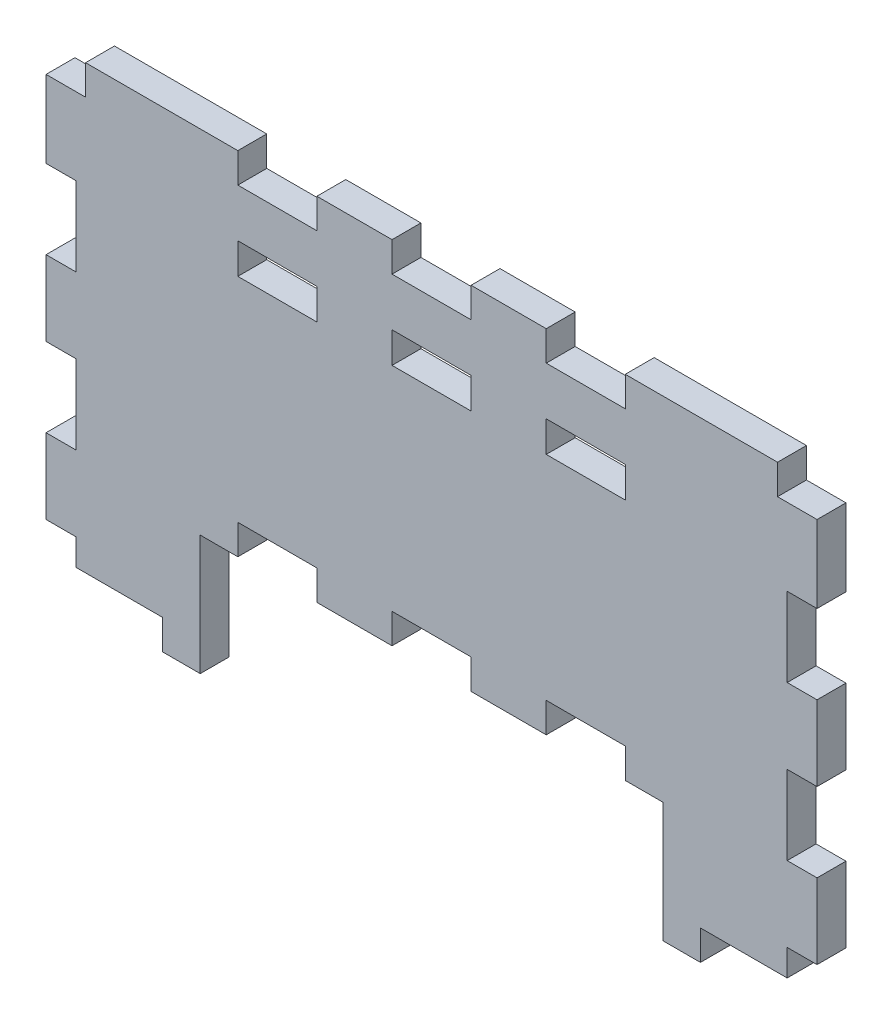
SolidWorks part; units mm, degrees
ref_plane "Front Plane" through (0, 0, 0) normal (0, 0, 1) x (1, 0, 0)
ref_plane "Top Plane" through (0, 0, 0) normal (0, 1, 0) x (1, 0, 0)
ref_plane "Right Plane" through (0, 0, 0) normal (1, 0, 0) x (0, 0, -1)
sketch "Sketch1" plane through (0, 0, 0) normal (0, 0, 1) x (1, 0, 0)
  line L0 (80, 3.175) -> (0, 3.175) construction
  line L1 (0, 52.125) -> (80, 52.125)
  line L2 (0, 52.125) -> (0, 3.175)
  line L3 (0, 3.175) -> (80, 3.175) construction
  line L4 (80, 52.125) -> (80, 3.175)
  line L5 (80, 52.125) -> (0, 52.125) construction
  line L6 (0, 52.125) -> (0, 3.175) construction
  line L7 (80, 52.125) -> (80, 3.175) construction
  line L8 (3, 49.125) -> (77, 49.125) construction
  line L9 (77, 49.125) -> (77, 6.175) construction
  line L10 (3, 6.175) -> (77, 6.175) construction
  line L11 (3, 49.125) -> (3, 6.175) construction
  line L12 (77, 49.125) -> (3, 49.125) construction
  line L13 (0, 18.625) -> (80, 18.625) construction
  line L14 (0, 15.625) -> (80, 15.625) construction
  line L15 (0, 40.925) -> (80, 40.925) construction
  line L16 (0, 37.925) -> (80, 37.925) construction
  line L17 (0, 37.925) -> (80, 37.925) construction
  line L18 (0, 40.925) -> (80, 40.925) construction
  line L19 (0, 15.625) -> (80, 15.625) construction
  line L20 (80, 18.625) -> (0, 18.625) construction
  line L21 (16, 3.175) -> (16, 15.625)
  line L22 (16, 15.625) -> (64, 15.625)
  line L23 (64, 15.625) -> (64, 3.175)
  line L24 (16, 3.175) -> (16, 15.625) construction
  line L25 (64, 15.625) -> (64, 3.175) construction
  line L26 (16, 3.175) -> (0, 3.175)
  line L27 (64, 3.175) -> (80, 3.175)
  circle A0 centre (37.5, 29.175) radius 21 construction
  circle A1 centre (37.5, 29.175) radius 24 construction
  circle A2 centre (37.5, 29.175) radius 24 construction
  circle A3 centre (37.5, 29.175) radius 21 construction
sketch "Sketch2" plane through (0, 0, 0) normal (1, 0, 0) x (0, 0, -1)
  line L1 (0, 52.125) -> (3, 52.125)
  line L2 (0, 52.125) -> (0, 3.175)
  line L3 (0, 3.175) -> (3, 3.175)
  line L4 (3, 52.125) -> (3, 3.175)
extrude "Boss-Extrude1" add sketch "Sketch1" against normal up to vertex (3 mm away) up to point (0, 52.125, -3)
sketch "Sketch3" plane through (0, 0, 0) normal (0, 0, 1) x (1, 0, 0)
  line L4 (4.1, 52.225) -> (-0.1, 52.225)
  line L5 (-0.1, 52.225) -> (-0.1, 49.025)
  line L6 (-0.1, 49.025) -> (4.1, 49.025)
  line L7 (4.1, 49.025) -> (4.1, 52.225)
  line L8 (4, 52.125) -> (0, 52.125)
  line L9 (0, 52.125) -> (0, 49.125)
  line L10 (0, 49.125) -> (4, 49.125)
  line L11 (4, 49.125) -> (4, 52.125)
  line L12 (4, 52.125) -> (0, 52.125) construction
  line L13 (0, 52.125) -> (0, 49.125) construction
  line L14 (0, 49.125) -> (4, 49.125) construction
  line L15 (4, 49.125) -> (4, 52.125) construction
  line L16 (3, 16.925) -> (3, 24.925)
  line L17 (3, 24.925) -> (0, 24.925)
  line L18 (0, 24.925) -> (0, 16.925)
  line L19 (0, 16.925) -> (3, 16.925)
  line L20 (3, 16.925) -> (3, 24.925) construction
  line L21 (3, 24.925) -> (0, 24.925) construction
  line L22 (0, 24.925) -> (0, 16.925) construction
  line L23 (0, 16.925) -> (3, 16.925) construction
  line L24 (28, 18.625) -> (20, 18.625)
  line L25 (20, 18.625) -> (20, 15.625)
  line L26 (20, 15.625) -> (28, 15.625)
  line L27 (28, 15.625) -> (28, 18.625)
  line L28 (28, 18.625) -> (20, 18.625) construction
  line L29 (20, 18.625) -> (20, 15.625) construction
  line L30 (20, 15.625) -> (28, 15.625) construction
  line L31 (28, 15.625) -> (28, 18.625) construction
  line L32 (44, 18.625) -> (36, 18.625)
  line L33 (44, 15.625) -> (44, 18.625)
  line L34 (36, 15.625) -> (44, 15.625)
  line L35 (36, 18.625) -> (36, 15.625)
  line L36 (44, 18.625) -> (36, 18.625) construction
  line L37 (44, 15.625) -> (44, 18.625) construction
  line L38 (36, 15.625) -> (44, 15.625) construction
  line L39 (36, 18.625) -> (36, 15.625) construction
  line L40 (3, 32.925) -> (3, 40.925)
  line L41 (0, 32.925) -> (3, 32.925)
  line L42 (0, 40.925) -> (0, 32.925)
  line L43 (3, 40.925) -> (0, 40.925)
  line L44 (3, 32.925) -> (3, 40.925) construction
  line L45 (0, 32.925) -> (3, 32.925) construction
  line L46 (0, 40.925) -> (0, 32.925) construction
  line L47 (3, 40.925) -> (0, 40.925) construction
  line L48 (36, 49.125) -> (44, 49.125)
  line L49 (44, 49.125) -> (44, 52.125)
  line L50 (44, 52.125) -> (36, 52.125)
  line L51 (36, 52.125) -> (36, 49.125)
  line L52 (36, 49.125) -> (44, 49.125) construction
  line L53 (44, 49.125) -> (44, 52.125) construction
  line L54 (44, 52.125) -> (36, 52.125) construction
  line L55 (36, 52.125) -> (36, 49.125) construction
  line L56 (44, 43.925) -> (36, 43.925)
  line L57 (44, 40.925) -> (44, 43.925)
  line L58 (36, 40.925) -> (44, 40.925)
  line L59 (36, 43.925) -> (36, 40.925)
  line L60 (44, 43.925) -> (36, 43.925) construction
  line L61 (44, 40.925) -> (44, 43.925) construction
  line L62 (36, 40.925) -> (44, 40.925) construction
  line L63 (36, 43.925) -> (36, 40.925) construction
  line L64 (28, 43.925) -> (20, 43.925)
  line L65 (28, 40.925) -> (28, 43.925)
  line L66 (20, 40.925) -> (28, 40.925)
  line L67 (20, 43.925) -> (20, 40.925)
  line L68 (28, 43.925) -> (20, 43.925) construction
  line L69 (28, 40.925) -> (28, 43.925) construction
  line L70 (20, 40.925) -> (28, 40.925) construction
  line L71 (20, 43.925) -> (20, 40.925) construction
  line L72 (20, 49.125) -> (28, 49.125)
  line L73 (28, 49.125) -> (28, 52.125)
  line L74 (28, 52.125) -> (20, 52.125)
  line L78 (20, 52.125) -> (20, 49.125)
  line L79 (20, 49.125) -> (28, 49.125) construction
  line L80 (28, 49.125) -> (28, 52.125) construction
  line L82 (28, 52.125) -> (20, 52.125) construction
  line L83 (20, 52.125) -> (20, 49.125) construction
  line L84 (60, 40.925) -> (60, 43.925)
  line L85 (52, 40.925) -> (60, 40.925)
  line L86 (52, 43.925) -> (52, 40.925)
  line L87 (60, 43.925) -> (52, 43.925)
  line L88 (60, 40.925) -> (60, 43.925) construction
  line L89 (52, 40.925) -> (60, 40.925) construction
  line L90 (52, 43.925) -> (52, 40.925) construction
  line L91 (60, 43.925) -> (52, 43.925) construction
  line L92 (52, 18.625) -> (52, 15.625)
  line L93 (52, 15.625) -> (60, 15.625)
  line L94 (60, 15.625) -> (60, 18.625)
  line L95 (60, 18.625) -> (52, 18.625)
  line L96 (52, 18.625) -> (52, 15.625) construction
  line L97 (52, 15.625) -> (60, 15.625) construction
  line L98 (60, 15.625) -> (60, 18.625) construction
  line L99 (60, 18.625) -> (52, 18.625) construction
  line L100 (77, 40.925) -> (77, 32.925)
  line L101 (77, 32.925) -> (80, 32.925)
  line L102 (80, 32.925) -> (80, 40.925)
  line L106 (80, 40.925) -> (77, 40.925)
  line L107 (77, 40.925) -> (77, 32.925) construction
  line L108 (77, 32.925) -> (80, 32.925) construction
  line L110 (80, 32.925) -> (80, 40.925) construction
  line L111 (80, 40.925) -> (77, 40.925) construction
  line L112 (76, 52.125) -> (76, 49.125)
  line L113 (76, 49.125) -> (80, 49.125)
  line L114 (80, 49.125) -> (80, 52.125)
  line L115 (80, 52.125) -> (76, 52.125)
  line L116 (76, 52.125) -> (76, 49.125) construction
  line L117 (76, 49.125) -> (80, 49.125) construction
  line L118 (80, 49.125) -> (80, 52.125) construction
  line L119 (80, 52.125) -> (76, 52.125) construction
  line L120 (77, 24.925) -> (77, 16.925)
  line L121 (80, 24.925) -> (77, 24.925)
  line L122 (80, 16.925) -> (80, 24.925)
  line L123 (77, 16.925) -> (80, 16.925)
  line L124 (77, 24.925) -> (77, 16.925) construction
  line L125 (80, 24.925) -> (77, 24.925) construction
  line L126 (80, 16.925) -> (80, 24.925) construction
  line L127 (77, 16.925) -> (80, 16.925) construction
  line L128 (60, 49.125) -> (60, 52.125)
  line L129 (52, 49.125) -> (60, 49.125)
  line L130 (52, 52.125) -> (52, 49.125)
  line L131 (60, 52.125) -> (52, 52.125)
  line L134 (60, 49.125) -> (60, 52.125) construction
  line L135 (52, 49.125) -> (60, 49.125) construction
  line L136 (52, 52.125) -> (52, 49.125) construction
  line L137 (60, 52.125) -> (52, 52.125) construction
  line L138 (3.1, 16.825) -> (3.1, 25.025)
  line L139 (3.1, 25.025) -> (-0.1, 25.025)
  line L140 (77, 8.925) -> (77, 6.175)
  line L141 (77, 6.175) -> (68, 6.175)
  line L142 (68, 6.175) -> (68, 3.175)
  line L143 (68, 3.175) -> (80, 3.175)
  line L144 (80, 3.175) -> (80, 8.925)
  line L145 (80, 8.925) -> (77, 8.925)
  line L146 (77, 8.925) -> (77, 6.175) construction
  line L147 (77, 6.175) -> (68, 6.175) construction
  line L148 (68, 6.175) -> (68, 3.175) construction
  line L149 (68, 3.175) -> (80, 3.175) construction
  line L150 (80, 3.175) -> (80, 8.925) construction
  line L151 (80, 8.925) -> (77, 8.925) construction
  line L152 (3, 6.175) -> (3, 8.925)
  line L153 (3, 8.925) -> (0, 8.925)
  line L154 (0, 8.925) -> (0, 3.175)
  line L155 (0, 3.175) -> (12, 3.175)
  line L156 (12, 3.175) -> (12, 6.175)
  line L157 (12, 6.175) -> (3, 6.175)
  line L304 (3, 6.175) -> (3, 8.925) construction
  line L305 (3, 8.925) -> (0, 8.925) construction
  line L306 (0, 8.925) -> (0, 3.175) construction
  line L307 (0, 3.175) -> (12, 3.175) construction
  line L308 (12, 3.175) -> (12, 6.175) construction
  line L309 (12, 6.175) -> (3, 6.175) construction
  line L310 (-0.1, 25.025) -> (-0.1, 16.825)
  line L311 (-0.1, 16.825) -> (3.1, 16.825)
  line L312 (28.1, 18.725) -> (19.9, 18.725)
  line L313 (19.9, 18.725) -> (19.9, 15.525)
  line L314 (19.9, 15.525) -> (28.1, 15.525)
  line L315 (28.1, 15.525) -> (28.1, 18.725)
  line L316 (44.1, 18.725) -> (35.9, 18.725)
  line L317 (35.9, 18.725) -> (35.9, 15.525)
  line L318 (35.9, 15.525) -> (44.1, 15.525)
  line L319 (44.1, 15.525) -> (44.1, 18.725)
  line L320 (3.1, 32.825) -> (3.1, 41.025)
  line L321 (3.1, 41.025) -> (-0.1, 41.025)
  line L322 (-0.1, 41.025) -> (-0.1, 32.825)
  line L323 (-0.1, 32.825) -> (3.1, 32.825)
  line L324 (35.9, 49.025) -> (44.1, 49.025)
  line L325 (44.1, 49.025) -> (44.1, 52.225)
  line L326 (44.1, 52.225) -> (35.9, 52.225)
  line L327 (35.9, 52.225) -> (35.9, 49.025)
  line L328 (44.1, 44.025) -> (35.9, 44.025)
  line L329 (35.9, 44.025) -> (35.9, 40.825)
  line L330 (35.9, 40.825) -> (44.1, 40.825)
  line L331 (44.1, 40.825) -> (44.1, 44.025)
  line L332 (28.1, 44.025) -> (19.9, 44.025)
  line L333 (19.9, 44.025) -> (19.9, 40.825)
  line L334 (19.9, 40.825) -> (28.1, 40.825)
  line L335 (28.1, 40.825) -> (28.1, 44.025)
  line L336 (19.9, 49.025) -> (28.1, 49.025)
  line L337 (28.1, 49.025) -> (28.1, 52.225)
  line L338 (28.1, 52.225) -> (19.9, 52.225)
  line L339 (19.9, 52.225) -> (19.9, 49.025)
  line L340 (60.1, 40.825) -> (60.1, 44.025)
  line L341 (60.1, 44.025) -> (51.9, 44.025)
  line L342 (51.9, 44.025) -> (51.9, 40.825)
  line L343 (51.9, 40.825) -> (60.1, 40.825)
  line L344 (51.9, 18.725) -> (51.9, 15.525)
  line L345 (51.9, 15.525) -> (60.1, 15.525)
  line L346 (60.1, 15.525) -> (60.1, 18.725)
  line L347 (60.1, 18.725) -> (51.9, 18.725)
  line L348 (76.9, 41.025) -> (76.9, 32.825)
  line L349 (76.9, 32.825) -> (80.1, 32.825)
  line L350 (80.1, 32.825) -> (80.1, 41.025)
  line L351 (80.1, 41.025) -> (76.9, 41.025)
  line L352 (75.9, 52.225) -> (75.9, 49.025)
  line L353 (75.9, 49.025) -> (80.1, 49.025)
  line L354 (80.1, 49.025) -> (80.1, 52.225)
  line L355 (80.1, 52.225) -> (75.9, 52.225)
  line L356 (76.9, 25.025) -> (76.9, 16.825)
  line L357 (76.9, 16.825) -> (80.1, 16.825)
  line L358 (80.1, 16.825) -> (80.1, 25.025)
  line L359 (80.1, 25.025) -> (76.9, 25.025)
  line L360 (60.1, 49.025) -> (60.1, 52.225)
  line L361 (60.1, 52.225) -> (51.9, 52.225)
  line L362 (51.9, 52.225) -> (51.9, 49.025)
  line L363 (51.9, 49.025) -> (60.1, 49.025)
  line L364 (76.9, 9.025) -> (76.9, 6.275)
  line L365 (76.9, 6.275) -> (67.9, 6.275)
  line L366 (67.9, 6.275) -> (67.9, 3.075)
  line L367 (67.9, 3.075) -> (80.1, 3.075)
  line L368 (80.1, 3.075) -> (80.1, 9.025)
  line L369 (80.1, 9.025) -> (76.9, 9.025)
  line L370 (3.1, 6.275) -> (3.1, 9.025)
  line L371 (3.1, 9.025) -> (-0.1, 9.025)
  line L372 (-0.1, 9.025) -> (-0.1, 3.075)
  line L373 (-0.1, 3.075) -> (12.1, 3.075)
  line L374 (12.1, 3.075) -> (12.1, 6.275)
  line L375 (12.1, 6.275) -> (3.1, 6.275)
  dimension "D1" = 0
  dimension "D2" = 0
  dimension "D3" = 0
  dimension "D4" = 0
  dimension "D5" = 0
  dimension "D6" = 0
  dimension "D7" = 0
  dimension "D8" = 0
  dimension "D9" = 0
  dimension "D10" = 0
  dimension "D11" = 0
  dimension "D12" = 0
  dimension "D13" = 0
  dimension "D14" = 0
  dimension "D15" = 0
  dimension "D16" = 0
  dimension "D17" = 0
  dimension "D18" = 0.1
extrude "Cut-Extrude1" cut sketch "Sketch3" against normal through all
